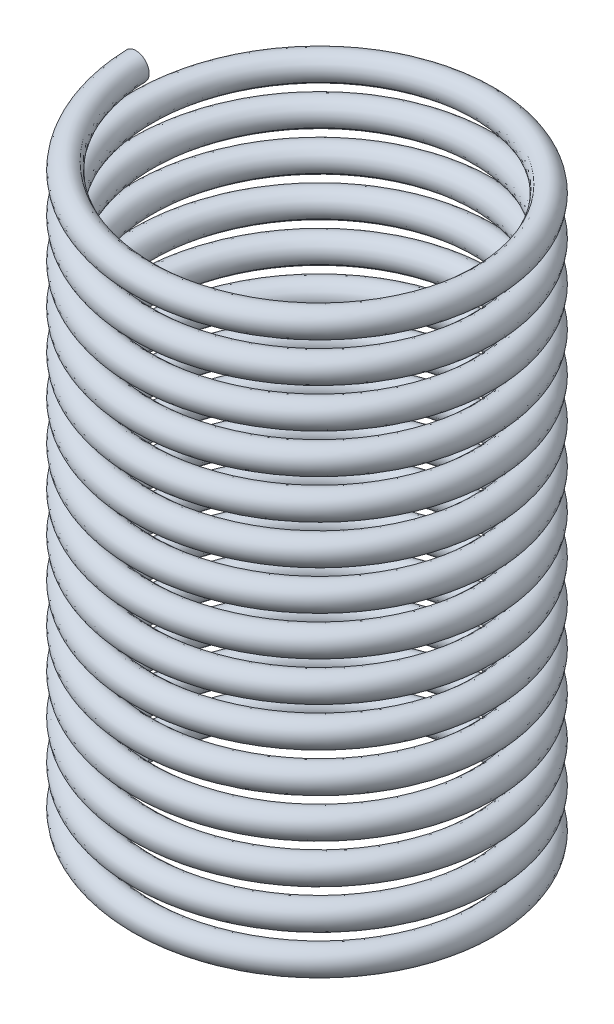
SolidWorks part; units mm, degrees
note: '?' marks a value the reader was unsure of.
ref_plane "前视基准面" through (0, 0, 0) normal (0, 0, 1) x (1, 0, 0)
ref_plane "上视基准面" through (0, 0, 0) normal (0, 1, 0) x (1, 0, 0)
ref_plane "右视基准面" through (0, 0, 0) normal (1, 0, 0) x (0, 0, -1)
sketch "草图1" plane through (0, 0, 0) normal (0, 1, 0) x (1, 0, 0)
  circle A0 centre (0, 0) radius 13
  dimension "D1" = 26
curve "螺旋线/涡状线1" pitch 3 height 45 radius 13 left hand yes centre (0, 0, 0) axis (0, 1, 0) start towards (0, 0, 1)
ref_axis "基准轴1" through (-13, 45, 0) along (0, 0, 1)?
sketch "草图5" plane through (0, 0, 0) normal (0, 0, 1) x (1, 0, 0)
  circle A0 centre (-13, 45) radius 1
  point P2 (-13, 45)
  point P6 (-13, 45)
  dimension "D1" = 2
sweep "扫描1" add profiles "草图5" path "螺旋线/涡状线1"
sketch "草图6" plane through (0, 0, 0) normal (0, 1, 0) x (1, 0, 0)
  circle A0 centre (0, 0) radius 30 construction
  dimension "D1" = 60
